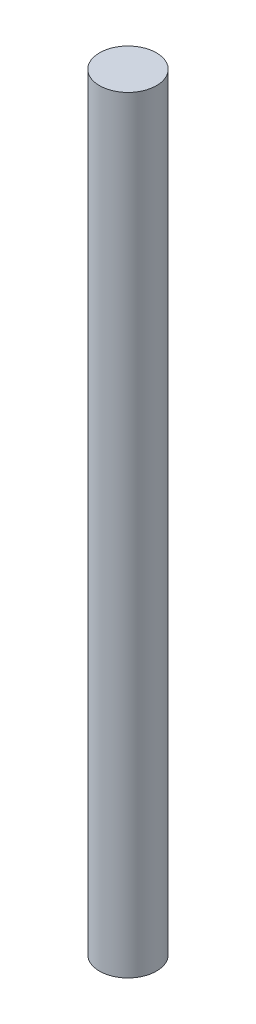
SolidWorks part; units mm, degrees
ref_plane "Front Plane" through (0, 0, 0) normal (0, 0, 1) x (1, 0, 0)
ref_plane "Top Plane" through (0, 0, 0) normal (0, 1, 0) x (1, 0, 0)
ref_plane "Right Plane" through (0, 0, 0) normal (1, 0, 0) x (0, 0, -1)
sketch "Sketch1" plane through (0, 0, 0) normal (0, 0, 1) x (1, 0, 0)
  line L0 (0, 0) -> (-6, 0)
  line L1 (-6, 0) -> (-6, 161.7)
  line L2 (-6, 161.7) -> (0, 161.7)
  line L3 (0, 161.7) -> (0, 0)
  line L4 (6, 0) -> (6, 161.7) construction
  line L5 (0, 161.7) -> (6, 161.7) construction
  line L6 (0, 0) -> (6, 0) construction
  line L7 (-1006, 80.85) -> (48994, 80.85) construction
  point P10 (-6, 80.85)
  dimension "D1" = 12
  dimension "D2" = 161.7
revolve "Revolve1" add sketch "Sketch1" angle 360 about L3
equation "\"ShaftDiameter\"= 12mm"
equation "\"D1@Sketch1\" = \"ShaftDiameter\""
equation "\"PendulumDiameter\"=12mm"
equation "\"PendulumLength\"= 140mm"
equation "\"EncoderOuterDiameter\"=1.5"
equation "\"EncoderShaftDiameter\"= 6mm"
equation "\"EncoderShaftLength\"=15mm+.5in+3mm"
equation "\"PendulumHolderangle\"=60"
equation "\"PendulumholderBottomHeight\"= 75"
equation "\"PendulumholderBottomWidth\"= 75"
equation "\"PendulumholderHeight\"=25"
equation "\"BearingOutsideDiameter\"=21mm"
equation "\"PendulumHolderWidth\"= 100mm"
equation "\"ShaftHeightFromTSlot\"= 100mm"
equation "\"BearingThickness\"= 5mm"
equation "\"SlipRingOuterDiameter\"=56mm"
equation "\"SlipringBigThickness\"=25mm"
equation "\"SlipringSmallThickness\"=8.5mm"
equation "\"Tol\"=2mm"
equation "\"ScrewHole\"= 5mm"
equation "\"Tframwidth\"= 40mm"
equation "\"TFrameheight\"= 12in"
equation "\"Tframetotalwidth\"= 2ft"
equation "\"TFramethickness\"= 6in"
equation "\"D2@Sketch1\"=\"TFramethickness\"-\"EncoderShaftLength\"+\"Tframwidth\""
